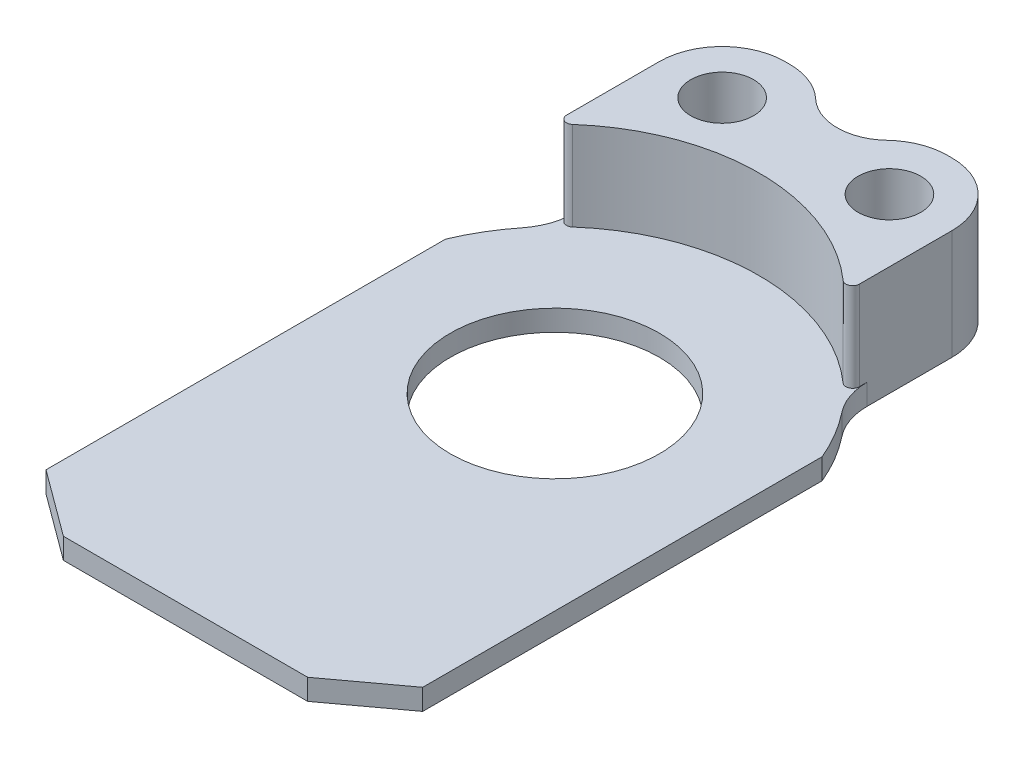
SolidWorks part; units mm, degrees
ref_plane "Front Plane" through (0, 0, 0) normal (0, 0, 1) x (1, 0, 0)
ref_plane "Top Plane" through (0, 0, 0) normal (0, 1, 0) x (1, 0, 0)
ref_plane "Right Plane" through (0, 0, 0) normal (1, 0, 0) x (0, 0, -1)
sketch "Sketch1" plane through (0, 0, 0) normal (0, 1, 0) x (1, 0, 0)
  line L1 (-14.3002, -24.3332) -> (-9.271, -28.0416)
  line L2 (-9.271, -28.0416) -> (9.271, -28.0416)
  line L3 (9.271, -28.0416) -> (14.3002, -24.3332)
  line L4 (14.3002, -24.3332) -> (14.3002, 5.9944)
  line L5 (-14.3002, 5.9944) -> (-14.3002, -24.3332)
  circle A0 centre (0, 0) radius 7.9375
  arc A2 (-14.3002, 5.9944) -> (14.3002, 5.9944) centre (0, 0) cw
  dimension "D1" = 15.875
  dimension "D2" = 28.0416
  dimension "D3" = 14.3002
  dimension "D5" = 5.0292
  dimension "D6" = 5.0292
  dimension "D7" = 3.7084
  dimension "D8" = 3.7084
  dimension "D9" = 34.036
  dimension "D10" = 34.036
extrude "Boss-Extrude1" add sketch "Sketch1" along normal blind 1.5875
sketch "Sketch2" plane through (0, 0, 0) normal (0, -1, 0) x (1, 0, 0)
  line L0 (-11.1125, -19.05) -> (-11.1125, -12.6011)
  line L1 (11.1125, -19.05) -> (11.1125, -12.6011)
  line L2 (-6.35, -23.8125) -> (-5.9834, -23.8125)
  line L3 (14.3002, 24.3332) -> (14.3002, -5.9944) construction
  line L4 (6.35, -23.8125) -> (5.9834, -23.8125)
  circle A0 centre (-6.35, -19.05) radius 2.3813
  circle A1 centre (6.35, -19.05) radius 2.3813
  arc A3 (-14.3002, -5.9944) -> (-12.1448, -9.6401) centre (0, 0) ccw
  arc A4 (-11.1125, -12.6011) -> (-12.1448, -9.6401) centre (-15.875, -12.6011) ccw
  arc A5 (12.1448, -9.6401) -> (14.3002, -5.9944) centre (0, 0) ccw
  arc A6 (12.1448, -9.6401) -> (11.1125, -12.6011) centre (15.875, -12.6011) ccw
  arc A7 (11.1125, -19.05) -> (6.35, -23.8125) centre (6.35, -19.05) cw
  arc A8 (-6.35, -23.8125) -> (-11.1125, -19.05) centre (-6.35, -19.05) cw
  arc A10 (-2.7174, -22.5162) -> (-5.9834, -23.8125) centre (-5.9834, -19.05) cw
  arc A11 (-2.7174, -22.5162) -> (2.7174, -22.5162) centre (0, -25.4) cw
  arc A12 (2.7174, -22.5162) -> (5.9834, -23.8125) centre (5.9834, -19.05) ccw
  arc M7 (-14.3002, -5.9944) -> (14.3002, -5.9944) centre (0, 0) ccw
  dimension "D5" = 4.7625
  dimension "D6" = 4.7625
  dimension "D10" = 4.7625
  dimension "D11" = 4.7625
  dimension "D12" = 4.7625
  dimension "D14" = 4.7625
  dimension "D15" = 4.7625
  dimension "D1" = 19.05
  dimension "D2" = 19.05
  dimension "D3" = 6.35
  dimension "D4" = 6.35
  dimension "D7" = 4.7625
  dimension "D8" = 4.7625
  dimension "D9" = 4.7625
  dimension "D13" = 25.4
extrude "Boss-Extrude2" add sketch "Sketch2" against normal blind 8.3344 contours A11 A12 L4 A7 L1 A6 A4 L0 A8 L2 A10 A0 A1 M7 region at (0, 0, -18.1634)
sketch "Sketch3" plane through (0, 8.3344, 0) normal (0, 1, 0) x (1, 0, 0)
  line L0 (-11.1125, 19.05) -> (-11.1125, 11.9994)
  line L1 (11.1125, 19.05) -> (11.1125, 11.9994)
  line L2 (-11.1125, 19.05) -> (-16.621, 6.8904)
  line L3 (-16.621, 6.8904) -> (16.4162, 6.3503)
  line L4 (16.4162, 6.3503) -> (11.1125, 19.05)
  arc A0 (12.1448, 9.6401) -> (-12.1448, 9.6401) centre (0, 0) ccw construction
  arc A1 (10.2681, 11.6187) -> (-10.2681, 11.6187) centre (0, 0) ccw
  arc A2 (11.1125, 11.9994) -> (10.2681, 11.6187) centre (10.6045, 11.9994) cw
  arc A3 (-11.1125, 11.9994) -> (-10.2681, 11.6187) centre (-10.6045, 11.9994) ccw
  point P12 (11.1125, 10.8139)
  point P15 (-11.1125, 10.8139)
  dimension "D1" = 0.508
extrude "Cut-Extrude1" cut sketch "Sketch3" against normal blind 6.7469
